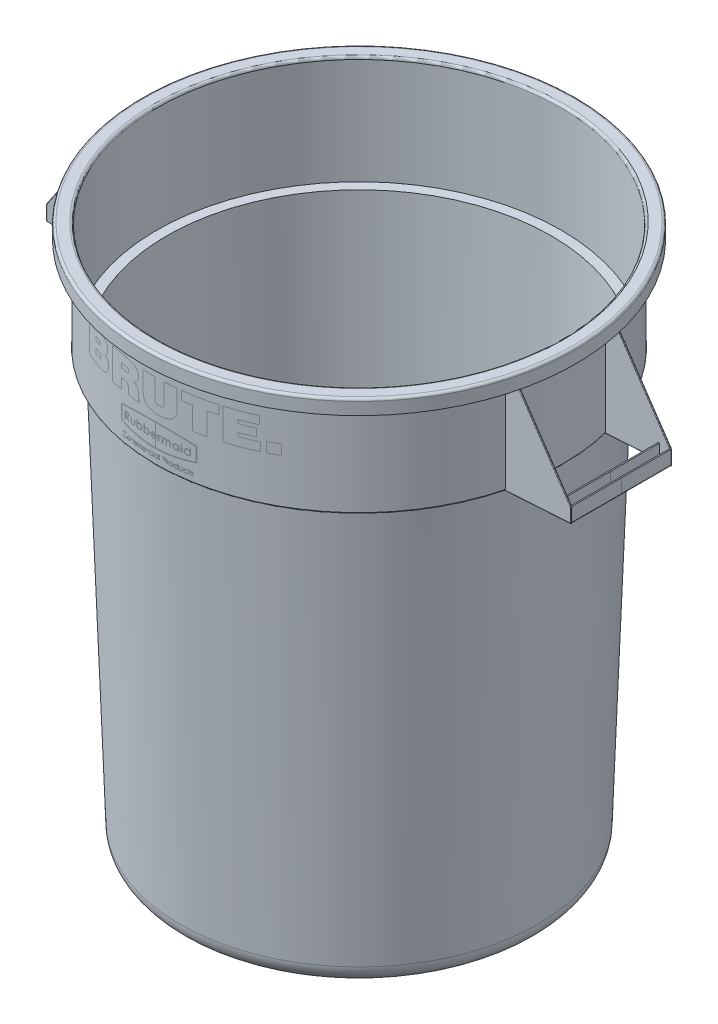
SolidWorks part; units mm, degrees
material "Plain Carbon Steel"
ref_plane "Front Plane" through (0, 0, 0) normal (0, 0, 1) x (1, 0, 0)
ref_plane "Top Plane" through (0, 0, 0) normal (0, 1, 0) x (1, 0, 0)
ref_plane "Center Plane" through (0, 0, 0) normal (1, 0, 0) x (0, 0, -1)
sketch "Sketch1" plane through (0, 0, 0) normal (0, 0, 1) x (1, 0, 0)
  line L0 (-158.75, 0) -> (-228.6, 0)
  line L1 (-228.6, 0) -> (-247.892, 552.45)
  line L2 (-260.592, 692.15) -> (-279.642, 692.15)
  line L3 (-279.642, 692.15) -> (-279.642, 673.1)
  line L4 (-158.75, 0) -> (-158.75, 34.925)
  line L5 (0, 0) -> (0, 802.8221) construction
  line L6 (-158.75, 34.925) -> (0, 34.925)
  line L7 (-247.892, 552.45) -> (-260.592, 552.45)
  line L8 (-260.592, 552.45) -> (-260.592, 692.15)
  line L9 (-157.1625, 33.3375) -> (0, 33.3375)
  line L10 (-157.1625, -1.5875) -> (-157.1625, 33.3375)
  line L11 (-157.1625, -1.5875) -> (-230.133, -1.5875)
  line L12 (-230.133, -1.5875) -> (-249.425, 550.8625)
  line L13 (-249.425, 550.8625) -> (-262.1795, 550.8625)
  line L14 (-262.1795, 550.8625) -> (-262.1795, 690.5625)
  line L15 (-262.1795, 690.5625) -> (-278.0545, 690.5625)
  line L16 (-278.0545, 690.5625) -> (-278.0545, 673.1)
  line L17 (-279.642, 673.1) -> (-278.0545, 673.1)
  line L18 (157.1625, 33.3375) -> (0, 33.3375)
  line L19 (158.75, 34.925) -> (0, 34.925)
  line L20 (279.642, 673.1) -> (278.0545, 673.1)
  line L21 (278.0545, 690.5625) -> (278.0545, 673.1)
  line L22 (262.1795, 690.5625) -> (278.0545, 690.5625)
  line L23 (262.1795, 550.8625) -> (262.1795, 690.5625)
  line L24 (249.425, 550.8625) -> (262.1795, 550.8625)
  line L25 (230.133, -1.5875) -> (249.425, 550.8625)
  line L26 (157.1625, -1.5875) -> (230.133, -1.5875)
  line L27 (157.1625, -1.5875) -> (157.1625, 33.3375)
  line L28 (260.592, 552.45) -> (260.592, 692.15)
  line L29 (247.892, 552.45) -> (260.592, 552.45)
  line L30 (158.75, 0) -> (158.75, 34.925)
  line L31 (279.642, 692.15) -> (279.642, 673.1)
  line L32 (260.592, 692.15) -> (279.642, 692.15)
  line L33 (228.6, 0) -> (247.892, 552.45)
  line L34 (158.75, 0) -> (228.6, 0)
  line L35 (-262.1795, 550.8625) -> (-338.3795, 555.997)
  line L36 (-338.3795, 555.997) -> (-338.3795, 575.047)
  line L37 (-338.3795, 575.047) -> (-279.642, 673.1)
  line L38 (-338.3795, 575.047) -> (-336.792, 575.047)
  line L39 (-336.792, 575.047) -> (-336.792, 557.5845)
  line L40 (-336.792, 557.5845) -> (-324.092, 557.5845)
  line L41 (-324.092, 557.5845) -> (-324.092, 575.047)
  line L42 (-324.092, 575.047) -> (-322.5045, 575.047)
  line L43 (-322.5045, 575.047) -> (-322.5045, 555.997)
  line L44 (-322.5045, 555.997) -> (-338.3795, 555.997)
  dimension "D2" = 692.15
  dimension "D3" = 19.05
  dimension "D4" = 92
  dimension "D5" = 19.05
  dimension "D6" = 69.85
  dimension "D7" = 34.925
  dimension "D8" = 12.7
  dimension "D9" = 139.7
  dimension "D11" = 76.2
  dimension "D12" = 114.3
  dimension "D13" = 19.05
  dimension "D14" = 1.5875
  dimension "D15" = 1.5875
  dimension "D16" = 1.5875
  dimension "D17" = 12.7
  dimension "D18" = 457.2
  dimension "D19" = 557.6965
  dimension "D10" = 1.5875
sketch "Sketch2" plane through (0, 0, 0) normal (0, 0, 1) x (1, 0, 0)
  line L0 (-279.642, 673.1) -> (-278.0545, 673.1) construction
  line L1 (-278.0545, 690.5625) -> (-278.0545, 673.1) construction
  line L2 (-279.642, 692.15) -> (-279.642, 673.1) construction
  line L3 (-262.1795, 690.5625) -> (-278.0545, 690.5625) construction
  line L4 (-260.592, 692.15) -> (-279.642, 692.15) construction
  line L5 (-260.592, 552.45) -> (-260.592, 692.15) construction
  line L6 (-262.1795, 550.8625) -> (-262.1795, 690.5625) construction
  line L7 (-249.425, 550.8625) -> (-262.1795, 550.8625) construction
  line L8 (-247.892, 552.45) -> (-260.592, 552.45) construction
  line L9 (-228.6, 0) -> (-247.892, 552.45) construction
  line L10 (-230.133, -1.5875) -> (-249.425, 550.8625) construction
  line L11 (-157.1625, -1.5875) -> (-230.133, -1.5875) construction
  line L12 (-158.75, 0) -> (-228.6, 0) construction
  line L13 (-158.75, 0) -> (-158.75, 34.925) construction
  line L14 (-157.1625, -1.5875) -> (-157.1625, 33.3375) construction
  line L15 (-158.75, 34.925) -> (0, 34.925) construction
  line L16 (-157.1625, 33.3375) -> (0, 33.3375) construction
  line L17 (-279.642, 673.1) -> (-278.0545, 673.1)
  line L18 (-278.0545, 690.5625) -> (-278.0545, 673.1)
  line L19 (-279.642, 692.15) -> (-279.642, 673.1)
  line L20 (-262.1795, 690.5625) -> (-278.0545, 690.5625)
  line L21 (-260.592, 692.15) -> (-279.642, 692.15)
  line L22 (-260.592, 552.45) -> (-260.592, 692.15)
  line L23 (-262.1795, 550.8625) -> (-262.1795, 690.5625)
  line L24 (-249.425, 550.8625) -> (-262.1795, 550.8625)
  line L25 (-247.892, 552.45) -> (-260.592, 552.45)
  line L26 (-228.6, 0) -> (-247.892, 552.45)
  line L27 (-230.133, -1.5875) -> (-249.425, 550.8625)
  line L28 (-157.1625, -1.5875) -> (-230.133, -1.5875)
  line L29 (-158.75, 0) -> (-228.6, 0)
  line L30 (-158.75, 0) -> (-158.75, 34.925)
  line L31 (-157.1625, -1.5875) -> (-157.1625, 33.3375)
  line L32 (-158.75, 34.925) -> (0, 34.925)
  line L33 (-157.1625, 33.3375) -> (0, 33.3375)
  line L34 (0, 34.925) -> (0, 33.3375)
revolve "Revolve2" add sketch "Sketch2" angle 360 about L5
fillet "Fillet3" radius 3.175 8 edges at (0, 692.15, -260.592) (0, 692.15, -279.642) (0, 690.5625, -278.0545) (0, 690.5625, -262.1795) (0, 0, -158.75) (0, 34.925, -158.75) (0, 33.3375, -157.1625) (0, -1.5875, -157.1625)
fillet "Fillet4" radius 25.4 2 edges at (0, -1.5875, -230.133) (0, 0, -228.6)
ref_plane "Plane1" through (0, 0, 63.5) normal (0, 0, 1) x (1, 0, 0)
sketch "Sketch3" plane through (0, 0, 63.5) normal (0, 0, 1) x (1, 0, 0)
  line L3 (-324.092, 557.5845) -> (-324.092, 575.047) construction
  line L4 (-324.092, 575.047) -> (-322.5045, 575.047) construction
  line L5 (-322.5045, 575.047) -> (-322.5045, 555.997) construction
  line L6 (-322.5045, 555.997) -> (-338.3795, 555.997) construction
  line L7 (-336.792, 557.5845) -> (-324.092, 557.5845) construction
  line L8 (-336.792, 575.047) -> (-336.792, 557.5845) construction
  line L9 (-338.3795, 555.997) -> (-338.3795, 575.047) construction
  line L10 (-338.3795, 575.047) -> (-336.792, 575.047) construction
  line L11 (-324.092, 557.5845) -> (-324.092, 575.047)
  line L12 (-324.092, 575.047) -> (-322.5045, 575.047)
  line L13 (-322.5045, 575.047) -> (-322.5045, 555.997)
  line L14 (-322.5045, 555.997) -> (-338.3795, 555.997)
  line L15 (-336.792, 557.5845) -> (-324.092, 557.5845)
  line L16 (-336.792, 575.047) -> (-336.792, 557.5845)
  line L17 (-338.3795, 555.997) -> (-338.3795, 575.047)
  line L18 (-338.3795, 575.047) -> (-336.792, 575.047)
extrude "Boss-Extrude1" add sketch "Sketch3" against normal up to surface (63.5 mm away) separate body up to plane "Front Plane"
sketch "Sketch5" plane through (-338.3795, 0, 0) normal (-1, 0, 0) x (0, 0, 1)
  line L0 (0, 550.8625) -> (63.5, 550.8625) construction
  line L1 (63.5, 550.8625) -> (65.0875, 550.8625)
  line L2 (63.5, 550.8625) -> (63.5, 673.1)
  line L3 (63.5, 673.1) -> (65.0875, 673.1)
  line L4 (65.0875, 550.8625) -> (65.0875, 673.1)
  line L5 (-249.425, 550.8625) -> (249.425, 550.8625) construction
  line L6 (0, 673.1) -> (63.5, 673.1) construction
  line L7 (0, 692.15) -> (0, 673.1) construction
  line L8 (63.5, 575.047) -> (63.5, 555.997) construction
  line L9 (0, 550.8625) -> (0, 690.5625) construction
  dimension "D2" = 1.5875
extrude "Boss-Extrude3" add sketch "Sketch5" against normal up to surface (84.0061 mm away) separate body up to face at (0, 687.3875, 262.1795)
sketch "Sketch6" plane through (0, 0, 65.0875) normal (0, 0, 1) x (1, 0, 0)
  line L0 (-253.9718, 550.8625) -> (-338.3795, 555.997)
  line L1 (-338.3795, 555.997) -> (-338.3795, 550.8625)
  line L2 (-338.3795, 550.8625) -> (-253.9718, 550.8625)
  line L3 (-338.3795, 575.047) -> (-338.3795, 673.1)
  line L4 (-338.3795, 673.1) -> (-271.9619, 673.1)
  line L5 (-271.9619, 673.1) -> (-338.3795, 575.047)
  line L6 (-279.642, 673.1) -> (279.642, 673.1) construction
extrude "Cut-Extrude1" cut sketch "Sketch6" against normal up to surface (1.5875 mm away) up to face at (-296.3764, 611.9813, 63.5)
fillet "Fillet7" radius 1.5875 4 edges at (-336.792, 557.5845, 31.75) (-324.092, 557.5845, 31.75) (-322.5045, 555.997, 31.75) (-338.3795, 555.997, 31.75)
fillet "Fillet11" radius 1.5875 1 edges at (0, 550.8625, -262.1795)
fillet "Fillet12" radius 0.7937 5 edges at (-296.3764, 553.4419, 63.5) (-296.1757, 553.4297, 65.0875) (-305.1707, 624.0735, 63.5) (-305.1707, 624.0735, 65.0875) (-338.3795, 565.522, 65.0875)
mirror "Mirror11" about plane through (0, 0, 0) normal (0, 0, 1) of bodies 108 106
mirror "Mirror12" about plane through (0, 0, 0) normal (1, 0, 0) of bodies 108 106 112 111
sketch "Sketch10" plane through (0, 0, 0) normal (0, 0, 1) x (1, 0, 0)
  text T0 "<b>BRUTE.</b>" font "Swis721 Blk BT" height in points 150
wrap "Wrap1" sketch "Sketch10" wrap type scribe source sketch "Sketch10" face at (0, 552.45, 262.1795)
sketch "Sketch11" plane through (0, 0, 0) normal (0, 0, 1) x (1, 0, 0)
  line L0 (48.9066, 594.3053) -> (48.9066, 575.4018)
  line L1 (-48.7265, 594.3053) -> (-48.7265, 575.4018)
  line L2 (48.1128, 593.6701) -> (48.1128, 576.0497)
  line L3 (-47.9328, 593.6564) -> (-47.9328, 576.0151)
  line L4 (-48.644, 575.3802) -> (-47.8327, 575.9893)
  line L5 (-48.7265, 575.4018) -> (-47.9328, 576.0151)
  spline S0 degree 3 poles (-48.7265, 594.3053) (-32.7583, 597.5609) (0.0041, 601.6281) (32.8422, 597.9377) (48.9066, 594.3053) knots 0 0 0 0 0.497603 1 1 1 1
  spline S1 degree 3 poles (-48.644, 575.3802) (-42.3882, 573.7414) (-26.3592, 570.5267) (6.5271, 568.4947) (32.784, 572.0981) (48.9066, 575.4018) knots 0.000866 0.000866 0.000866 0.000866 0.197761 0.498006 1 1 1 1
  spline S4 degree 3 poles (-47.9328, 593.6564) (-32.1407, 596.8418) (-7.9532, 599.796) (24.3071, 598.079) (40.2463, 595.4252) (48.1128, 593.6701) knots 0.006613 0.006613 0.006613 0.006613 0.500071 0.7468 0.993529 0.993529 0.993529 0.993529
  spline S5 degree 3 poles (48.1128, 576.0497) (40.1953, 574.4383) (24.2366, 571.743) (0.0438, 569.9504) (-24.1758, 571.096) (-40.0599, 573.9826) (-47.8327, 575.9893) knots 0.006239 0.006239 0.006239 0.006239 0.253031 0.499822 0.746614 0.992351 0.992351 0.992351 0.992351
  dimension "D1" = 18.9035
  dimension "D2" = 97.6331
  dimension "D3" = 26.6544
  dimension "D4" = 30.0495
  dimension "D5" = 26.0563
  dimension "D6" = 22.5767
  dimension "D7" = 49.0408
  dimension "D8" = 78.1962
sketch "Sketch13" plane through (0, 0, 0) normal (0, 0, 1) x (1, 0, 0)
  text T0 "Commercial Products" font "Century Gothic" height 6.35
sketch "Sketch14" plane through (0, 0, 0) normal (0, 0, 1) x (1, 0, 0)
  text T0 "Rubbermaid" font "Century Gothic" height 9.525
wrap "Wrap5" sketch "Sketch13" wrap type scribe source sketch "Sketch13" face at (97.3024, 629.56, 243.2462)
wrap "Wrap6" sketch "Sketch14" wrap type scribe source sketch "Sketch14" face at (40.1827, 563.0448, 259.0811)
wrap "Wrap7" sketch "Sketch11" wrap type scribe source sketch "Sketch11" face at (39.6994, 583.7258, 259.1463)
pattern_linear "LPattern1" [suppressed] count 2 spacing 139.7 along (0, 1, 0) of bodies 113 114 115 116 106 112 111 108 105
equation "\"Weight(KG)\"=\"Weight\"*0.453"
